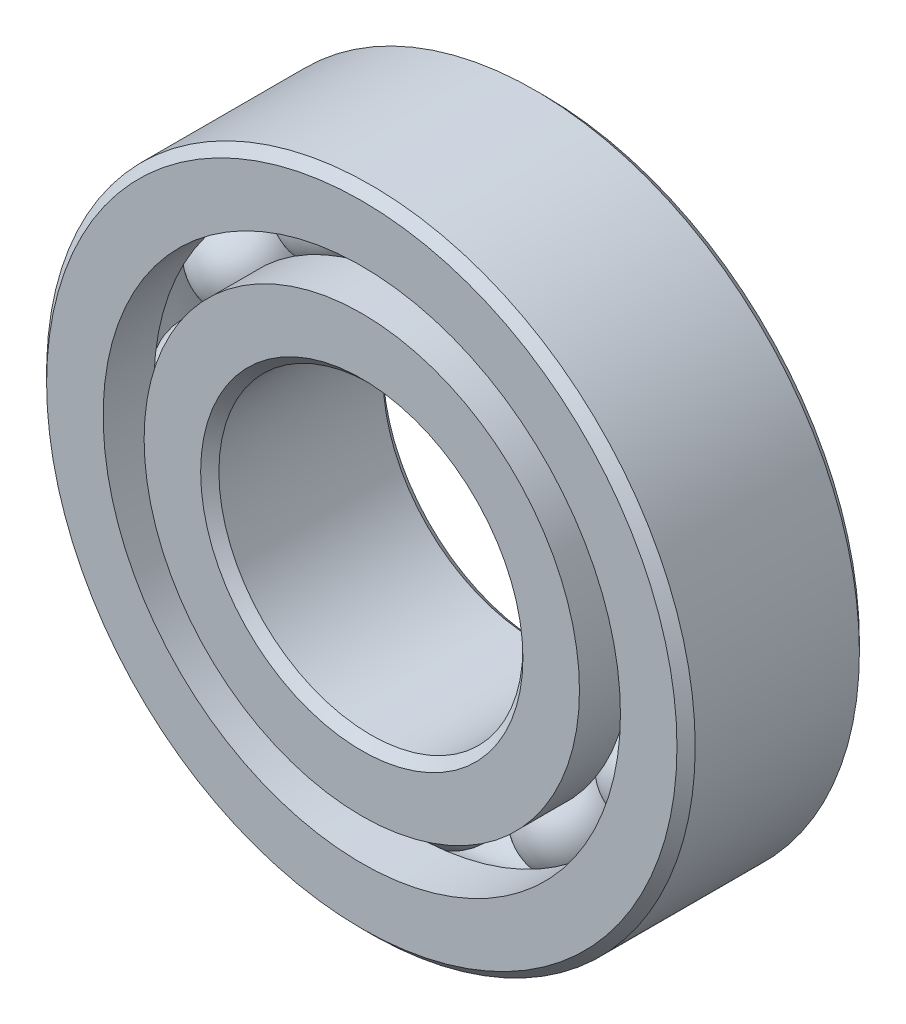
SolidWorks part; units mm, degrees
ref_plane "Front Plane" through (0, 0, 0) normal (0, 0, 1) x (1, 0, 0)
ref_plane "Top Plane" through (0, 0, 0) normal (0, 1, 0) x (1, 0, 0)
ref_plane "Right Plane" through (0, 0, 0) normal (1, 0, 0) x (0, 0, -1)
sketch "Sketch1" plane through (0, 0, 0) normal (1, 0, 0) x (0, 0, -1)
  line L0 (-4.5, 0) -> (4.5, 0) construction
  line L1 (0, 16) -> (0, -16) construction
  line L2 (4.05, 16) -> (-4.05, 16)
  line L3 (-4.05, 16) -> (-4.5, 15.55)
  line L4 (-4.5, 15.55) -> (-4.5, 12.761)
  line L5 (-4.5, 12.761) -> (-2, 12.761)
  line L6 (4.5, 12.761) -> (2, 12.761)
  line L7 (4.5, 15.55) -> (4.5, 12.761)
  line L8 (4.05, 16) -> (4.5, 15.55)
  line L9 (0, 16) -> (0, 11.75) construction
  line L10 (0, 11.75) -> (0, 7.5) construction
  arc A0 (-2, 12.761) -> (2, 12.761) centre (0, 11.75) cw
  point P14 (0, 7.5)
  dimension "Width" = 9
  dimension "OD" = 32
  dimension "D1" = 45
  dimension "D2" = 0.45
  dimension "Shaft Dia" = 15
  dimension "D3" = 4
  dimension "D4" = 1.011
revolve "Revolve1" add sketch "Sketch1" angle 360 about L0
sketch "Sketch3" plane through (0, 0, 0) normal (1, 0, 0) x (0, 0, -1)
  line L0 (-4.5, 10.739) -> (-2, 10.739)
  line L1 (0, 16) -> (0, -16) construction
  line L2 (-4.5, 15.55) -> (-4.5, 12.761) construction
  line L3 (-4.5, 10.739) -> (-4.5, 7.95)
  line L4 (-4.05, 16) -> (-4.5, 15.55) construction
  line L5 (-4.5, 7.95) -> (-4.05, 7.5)
  line L6 (-4.05, 7.5) -> (4.05, 7.5)
  line L7 (4.05, 16) -> (4.05, -16) construction
  line L8 (4.05, 7.5) -> (4.5, 7.95)
  line L9 (4.5, -15.55) -> (4.5, 15.55) construction
  line L10 (4.5, 7.95) -> (4.5, 10.739)
  line L11 (4.5, 10.739) -> (2, 10.739)
  line L13 (4.05, 16) -> (4.5, 15.55) construction
  arc A0 (2, 12.761) -> (-2, 12.761) centre (0, 11.75) ccw construction
  arc A1 (2, 10.739) -> (-2, 10.739) centre (0, 11.75) cw
revolve "Revolve3" add sketch "Sketch3" angle 360 about L0
sketch "Sketch4" plane through (0, 0, 0) normal (1, 0, 0) x (0, 0, -1)
  line L0 (-2.241, 11.75) -> (2.241, 11.75)
  arc A2 (-2.241, 11.75) -> (2.241, 11.75) centre (0, 11.75) cw
  arc A3 (2, 12.761) -> (-2, 12.761) centre (0, 11.75) ccw construction
revolve "Revolve4" add sketch "Sketch4" angle 360 about L0
ref_axis "Axis1" through (0, 0, -4.5) along (0, 0, 1)
pattern_circular "CirPattern1" count 12 every 30 about axis through (0, 0, -4.5) along (0, 0, 1) of bodies 104
sketch "Sketch5" plane through (0, 0, 0) normal (1, 0, 0) x (0, 0, -1)
  line L0 (-4.5, 12.761) -> (-2, 12.761) construction
  line L1 (-4.275, 12.761) -> (-2.241, 12.761)
  line L2 (-4.275, 12.761) -> (-4.275, 10.739)
  line L3 (-4.275, 10.739) -> (-2.241, 10.739)
  line L4 (-2.241, 12.761) -> (-2.241, 10.739)
  line L5 (-4.5, 10.739) -> (-2, 10.739) construction
  line L6 (4.5, 12.761) -> (2, 12.761) construction
  line L7 (4.275, 12.761) -> (2.241, 12.761)
  line L8 (4.275, 12.761) -> (4.275, 10.739)
  line L9 (4.275, 10.739) -> (2.241, 10.739)
  line L10 (2.241, 12.761) -> (2.241, 10.739)
  line L11 (4.5, 10.739) -> (2, 10.739) construction
  line L12 (-4.05, 16) -> (-4.5, 15.55) construction
  point P18 (-4.275, 15.775)
equation "\"D2@Sketch1\" = \"Width@Sketch1\"*.05"
equation "\"D3@Sketch1\" = \"Width@Sketch1\"/2.25"
equation "\"D4@Sketch1\" = (((\"OD@Sketch1\"-\"Width@Sketch1\")/2)/3.25)/3.5"
equation "\"D2@CirPattern1\" = 360/\"Balls@CirPattern1\""
